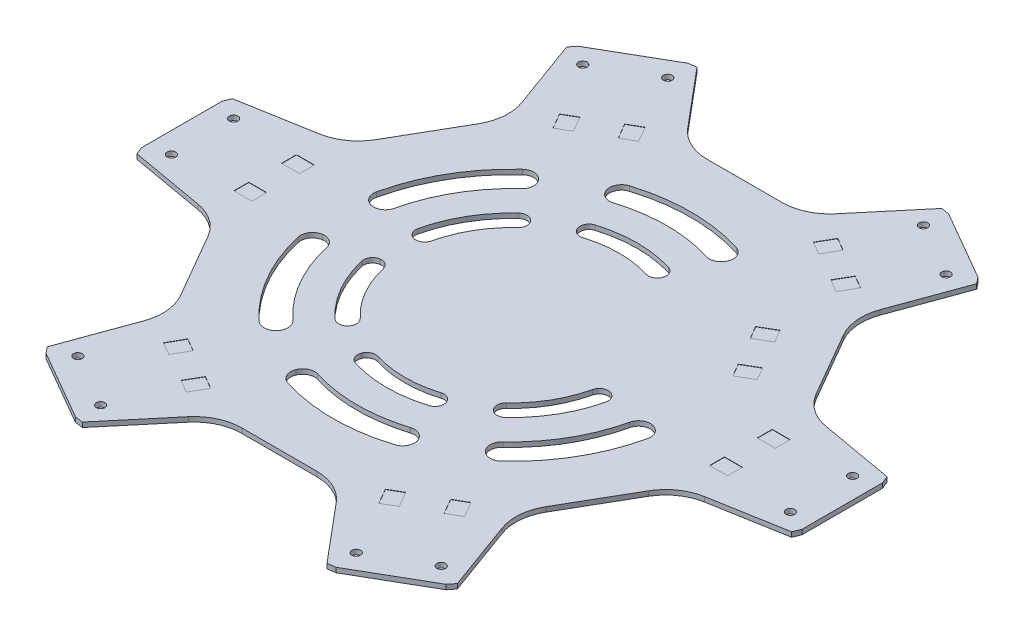
SolidWorks part; units mm, degrees
ref_plane "Front Plane" through (0, 0, 0) normal (0, 0, 1) x (1, 0, 0)
ref_plane "Top Plane" through (0, 0, 0) normal (0, 1, 0) x (1, 0, 0)
ref_plane "Right Plane" through (0, 0, 0) normal (1, 0, 0) x (0, 0, -1)
sketch "Sketch2" plane through (0, 0, 0) normal (0, 1, 0) x (1, 0, 0)
  line L0 (-110.75, -13.5) -> (-110.75, 13.5)
  line L1 (110.75, 0) -> (55.375, 95.9123) construction
  line L2 (55.375, 95.9123) -> (-55.375, 95.9123) construction
  line L3 (-55.375, 95.9123) -> (-110.75, 0) construction
  line L4 (-110.75, 0) -> (-55.375, -95.9123) construction
  line L5 (-55.375, -95.9123) -> (55.375, -95.9123) construction
  line L6 (55.375, -95.9123) -> (110.75, 0) construction
  line L7 (-110.75, 0) -> (0, 0) construction
  line L14 (0, 0) -> (0, 78) construction
  line L15 (-67.55, 39) -> (-90.0666, 0) construction
  line L16 (0, 78) -> (-67.55, 39) construction
  line L17 (-67.55, 39) -> (-67.55, -39) construction
  line L18 (-67.55, -39) -> (0, -78) construction
  line L19 (0, -78) -> (67.55, -39) construction
  line L20 (67.55, -39) -> (67.55, 39) construction
  line L21 (67.55, 39) -> (0, 78) construction
  line L22 (-110.75, 13.5) -> (-109.75, 13.5) construction
  line L23 (-67.55, 39) -> (-77.5583, 21.6651)
  line L24 (-109.75, 13.5) -> (-109.75, 16) construction
  line L25 (-110.75, 13.5) -> (-109.75, 16)
  line L26 (-77.5583, 21.6651) -> (-78.8083, 19.5) construction
  line L27 (-109.75, 16) -> (-77.5583, 21.6651)
  line L28 (-110.75, -13.5) -> (-109.75, -16)
  line L29 (-109.75, -16) -> (-77.5583, -21.6651)
  line L30 (-67.55, -39) -> (-77.5583, -21.6651)
  line L31 (-67.55, 39) -> (-57.5417, 56.3349)
  line L32 (-68.7314, 87.0463) -> (-57.5417, 56.3349)
  line L33 (-67.0663, 89.1623) -> (-68.7314, 87.0463)
  line L34 (-67.0663, 89.1623) -> (-43.6837, 102.6623)
  line L35 (-43.6837, 102.6623) -> (-41.0186, 103.0463)
  line L36 (-41.0186, 103.0463) -> (-20.0167, 78)
  line L37 (0, 78) -> (-20.0167, 78)
  line L38 (0, 78) -> (20.0167, 78)
  line L39 (41.0186, 103.0463) -> (20.0167, 78)
  line L40 (43.6837, 102.6623) -> (41.0186, 103.0463)
  line L41 (43.6837, 102.6623) -> (67.0663, 89.1623)
  line L42 (67.0663, 89.1623) -> (68.7314, 87.0463)
  line L43 (68.7314, 87.0463) -> (57.5417, 56.3349)
  line L44 (67.55, 39) -> (57.5417, 56.3349)
  line L45 (67.55, 39) -> (77.5583, 21.6651)
  line L46 (109.75, 16) -> (77.5583, 21.6651)
  line L47 (110.75, 13.5) -> (109.75, 16)
  line L48 (110.75, 13.5) -> (110.75, -13.5)
  line L49 (110.75, -13.5) -> (109.75, -16)
  line L50 (109.75, -16) -> (77.5583, -21.6651)
  line L51 (67.55, -39) -> (77.5583, -21.6651)
  line L52 (67.55, -39) -> (57.5417, -56.3349)
  line L53 (68.7314, -87.0463) -> (57.5417, -56.3349)
  line L54 (67.0663, -89.1623) -> (68.7314, -87.0463)
  line L55 (67.0663, -89.1623) -> (43.6837, -102.6623)
  line L56 (43.6837, -102.6623) -> (41.0186, -103.0463)
  line L57 (41.0186, -103.0463) -> (20.0167, -78)
  line L58 (0, -78) -> (20.0167, -78)
  line L59 (0, -78) -> (-20.0167, -78)
  line L60 (-41.0186, -103.0463) -> (-20.0167, -78)
  line L61 (-43.6837, -102.6623) -> (-41.0186, -103.0463)
  line L62 (-43.6837, -102.6623) -> (-67.0663, -89.1623)
  line L63 (-67.0663, -89.1623) -> (-68.7314, -87.0463)
  line L64 (-68.7314, -87.0463) -> (-57.5417, -56.3349)
  line L65 (-67.55, -39) -> (-57.5417, -56.3349)
  circle A0 centre (0, 0) radius 95.9123 construction
  circle A1 centre (0, 0) radius 67.55 construction
  point P67 (0, 0)
  dimension "D1" = 110.75
  dimension "D2" = 13.5
  dimension "D3" = 78
  dimension "D4" = 1
  dimension "D5" = 2.5
  dimension "D6" = 2.5
  dimension "D7" = 6
extrude "Base plate" add sketch "Sketch2" along normal blind 1.6 contours L30 L65 L64 L63 L62 L61 L60 L59 L58 L57 L56 L55 L54 L53 L52 L51 L50 L49 L48 L47 L46 L45 L44 L43 L42 L41 L40 L39 L38 L37 L36 L35 L34 L33 L32 L31 L23 L27 L25 L0 L28 L29 region at (0, 0, 0)
fillet "Fillet3" radius 16 12 edges at (-57.5417, 0.8, 56.3349) (-77.5583, 0.8, 21.6651) (-20.0167, 0.8, 78) (20.0167, 0.8, 78) (57.5417, 0.8, 56.3349) (77.5583, 0.8, 21.6651) (77.5583, 0.8, -21.6651) (57.5417, 0.8, -56.3349) (20.0167, 0.8, -78) (-20.0167, 0.8, -78) (-57.5417, 0.8, -56.3349) (-77.5583, 0.8, -21.6651)
sketch "Sketch3" plane through (0, 1.6, 0) normal (0, 1, 0) x (1, 0, 0)
  line L0 (-55.375, 95.9123) -> (-64.4076, 90.6973) construction
  line L1 (-67.0663, 89.1623) -> (-43.6837, 102.6623) construction
  line L2 (-64.4076, 90.6973) -> (-60.9076, 84.6351) construction
  line L3 (-55.375, 95.9123) -> (-46.3424, 101.1273) construction
  line L4 (-46.3424, 101.1273) -> (-42.8424, 95.0651) construction
  dimension "D3" = 10.43
  dimension "D4" = 7
hole_wizard "M3.5x0.6 Tapped Hole2" positions "Sketch4" profile "Sketch5" tap size "M3.5x0.6" standard "ANSI Metric"
sketch "Sketch4" plane through (0, 1.6, 0) normal (0, 1, 0) x (1, 0, 0)
  point P0 (-60.9076, 84.6351)
  point P3 (-42.8424, 95.0651)
sketch "Sketch5" plane through (-60.9076, 1.6, -84.6351) normal (1, 0, 0) x (0, 0, 1)
  line L0 (0, 0) -> (0, 9.6712)
  line L1 (0, 9.6712) -> (1.45, 8.8)
  line L2 (1.45, 8.8) -> (1.45, 0)
  line L5 (1.45, 0) -> (0, 0)
  line L10 (0, 9.6712) -> (-1.45, 8.8) construction
  line L11 (0, -6.35) -> (0, 107.95) construction
  dimension "Tap Drill Dia." = 2.9
  dimension "Tap Drill Depth" = 8.8
  dimension "Drill Angle" = 118
sketch "Sketch6" plane through (0, 0, 0) normal (1, 0, 0) x (0, 0, -1)
  line L0 (0, 0) -> (0, 50) construction
  dimension "D1" = 50
pattern_circular "CirPattern1" count 6 over 360 about axis through (0, 0, 0) along (0, 1, 0) of "M3.5x0.6 Tapped Hole2"
sketch "Sketch7" plane through (0, 1.6, 0) normal (0, 1, 0) x (1, 0, 0)
  line L0 (0, 52) -> (0, 60) construction
  line L1 (20.5, 52.1129) -> (19.0357, 48.3905)
  line L3 (0, 56) -> (-20.5, 56) construction
  line L4 (20.5, 52.1129) -> (21.9643, 55.8352)
  line L5 (0, 52) -> (0, 42) construction
  line L6 (-20.5, 52.1129) -> (-21.9643, 55.8352)
  line L7 (-20.5, 52.1129) -> (-19.0357, 48.3905)
  line L8 (0, 42) -> (0, 36) construction
  line L9 (-19.0357, 48.3905) -> (-15.375, 39.0846) construction
  line L10 (-15.375, 39.0846) -> (-13.1786, 33.5011)
  line L11 (15.375, 39.0846) -> (13.1786, 33.5011)
  arc A0 (21.9643, 55.8352) -> (-21.9643, 55.8352) centre (0, 0) ccw
  arc A1 (19.0357, 48.3905) -> (-19.0357, 48.3905) centre (0, 0) ccw
  arc A2 (0, 56) -> (-20.5, 52.1129) centre (0, 0) ccw construction
  arc A3 (15.375, 39.0846) -> (-15.375, 39.0846) centre (0, 0) ccw
  arc A4 (13.1786, 33.5011) -> (-13.1786, 33.5011) centre (0, 0) ccw
  dimension "D1" = 60
  dimension "D2" = 52
  dimension "D4" = 20.5
  dimension "D3" = 4
  dimension "D5" = 56
  dimension "D6" = 52
  dimension "D8" = 20.5
extrude "Cut-Extrude1" cut sketch "Sketch7" against normal up to next
fillet "Fillet4" radius 4 4 edges at (19.0357, 0.8, -48.3905) (21.9643, 0.8, -55.8352) (-19.0357, 0.8, -48.3905) (-21.9643, 0.8, -55.8352)
fillet "Fillet5" radius 3 4 edges at (13.1786, 0.8, -33.5011) (15.375, 0.8, -39.0846) (-13.1786, 0.8, -33.5011) (-15.375, 0.8, -39.0846)
pattern_circular "CirPattern2" count 5 every 60 about axis through (0, 0, 0) along (0, 1, 0) of "Cut-Extrude1", "Fillet4", "Fillet5"
sketch "Sketch8" plane through (0, 1.6, 0) normal (0, 1, 0) x (1, 0, 0)
  line L0 (-39.875, 69.0655) -> (0, 0) construction
  line L1 (-55.375, 95.9123) -> (-39.875, 69.0655) construction
  line L2 (-39.875, 69.0655) -> (-46.8032, 65.0655) construction
  line L3 (-46.8032, 65.0655) -> (-48.3032, 67.6636) construction
  line L4 (-48.3032, 67.6636) -> (-50.4683, 66.4136) construction
  line L5 (-50.4683, 66.4136) -> (-46.1381, 68.9136)
  line L6 (-46.1381, 68.9136) -> (-43.1381, 63.7174)
  line L7 (-43.1381, 63.7174) -> (-47.4683, 61.2174)
  line L8 (-47.4683, 61.2174) -> (-50.4683, 66.4136)
  line L9 (-33.6119, 69.2174) -> (-29.2817, 71.7174)
  line L10 (-36.6119, 74.4136) -> (-33.6119, 69.2174)
  line L11 (-32.2817, 76.9136) -> (-36.6119, 74.4136)
  line L12 (-29.2817, 71.7174) -> (-32.2817, 76.9136)
  dimension "D1" = 31
  dimension "D2" = 8
  dimension "D3" = 3
  dimension "D4" = 2.5
  dimension "D5" = 6
  dimension "D6" = 5
  dimension "D7" = 3
extrude "Cut-Extrude2" cut sketch "Sketch8" against normal blind 0.1
pattern_circular "CirPattern3" count 6 over 360 about axis through (0, 0, 0) along (0, 1, 0) of "Cut-Extrude2" reverse direction yes
sketch "Sketch9" plane through (0, 1.6, 0) normal (0, 1, 0) x (1, 0, 0)
  line L0 (67.55, 39) -> (51.9615, 30) construction
  line L1 (61.2738, 49.8707) -> (73.8262, 28.1293) construction
  line L2 (51.9615, 30) -> (47.9615, 36.9282) construction
  line L3 (47.9615, 36.9282) -> (45.3634, 35.4282) construction
  line L4 (45.3634, 35.4282) -> (44.1134, 37.5933) construction
  line L5 (44.1134, 37.5933) -> (49.3096, 40.5933)
  line L6 (49.3096, 40.5933) -> (51.8096, 36.2631)
  line L7 (51.8096, 36.2631) -> (46.6134, 33.2631)
  line L8 (46.6134, 33.2631) -> (44.1134, 37.5933)
  line L9 (59.8096, 22.4067) -> (57.3096, 26.7369)
  line L10 (57.3096, 26.7369) -> (52.1134, 23.7369)
  line L11 (52.1134, 23.7369) -> (54.6134, 19.4067)
  line L12 (54.6134, 19.4067) -> (59.8096, 22.4067)
  dimension "D1" = 18
  dimension "D2" = 8
  dimension "D3" = 6
  dimension "D4" = 5
  dimension "D5" = 3
  dimension "D6" = 2.5
extrude "Cut-Extrude3" cut sketch "Sketch9" against normal blind 0.1 contours L11 L12 L9 L10 | L8 L7 L6 L5 region at (47.9615, 1.6, -36.9282) region at (55.9615, 1.6, -23.0718)
sketch "Sketch11" plane through (-67.55, 0, 39) normal (-0.866, 0, 0.5) x (0.5, 0, 0.866)
  line L0 (0, 1.6) -> (0, 0) construction
  line L1 (12.5525, 1.6) -> (-12.5525, 1.6) construction
sketch "Sketch12" plane through (0, 0, 78) normal (0, 0, 1) x (1, 0, 0)
  line L0 (0, 1.6) -> (0, 0) construction
  line L1 (12.5525, 1.6) -> (-12.5525, 1.6) construction
  line L2 (12.5525, 0) -> (-12.5525, 0) construction
sketch "Sketch13" plane through (67.55, 0, 39) normal (0.866, 0, 0.5) x (0.5, 0, -0.866)
  line L0 (0, 1.6) -> (0, 0) construction
  line L1 (12.5525, 1.6) -> (-12.5525, 1.6) construction
  line L2 (12.5525, 0) -> (-12.5525, 0) construction
sketch "Sketch14" plane through (67.55, 0, -39) normal (0.866, 0, -0.5) x (-0.5, 0, -0.866)
  line L0 (0, 1.6) -> (0, 0) construction
  line L1 (12.5525, 1.6) -> (-12.5525, 1.6) construction
  line L2 (12.5525, 0) -> (-12.5525, 0) construction
sketch "Sketch15" plane through (0, 0, -78) normal (0, 0, -1) x (-1, 0, 0)
  line L0 (0, 1.6) -> (0, 0) construction
  line L1 (12.5525, 1.6) -> (-12.5525, 1.6) construction
  line L2 (12.5525, 0) -> (-12.5525, 0) construction
sketch "Sketch16" plane through (-67.55, 0, -39) normal (-0.866, 0, -0.5) x (-0.5, 0, 0.866)
  line L0 (0, 1.6) -> (0, 0) construction
  line L1 (12.5525, 1.6) -> (-12.5525, 1.6) construction
  line L2 (12.5525, 0) -> (-12.5525, 0) construction
sketch "Sketch17" plane through (0, 1.6, 0) normal (0, 1, 0) x (1, 0, 0)
  line L0 (67.55, 39) -> (-67.55, -39) construction
  line L1 (-61.2738, -49.8707) -> (-73.8262, -28.1293) construction
  line L2 (-67.55, 39) -> (67.55, -39) construction
  line L3 (-73.8262, 28.1293) -> (-61.2738, 49.8707) construction
  line L4 (0, 78) -> (0, -78) construction
  line L5 (-12.5525, 78) -> (12.5525, 78) construction
  line L6 (12.5525, -78) -> (-12.5525, -78) construction
